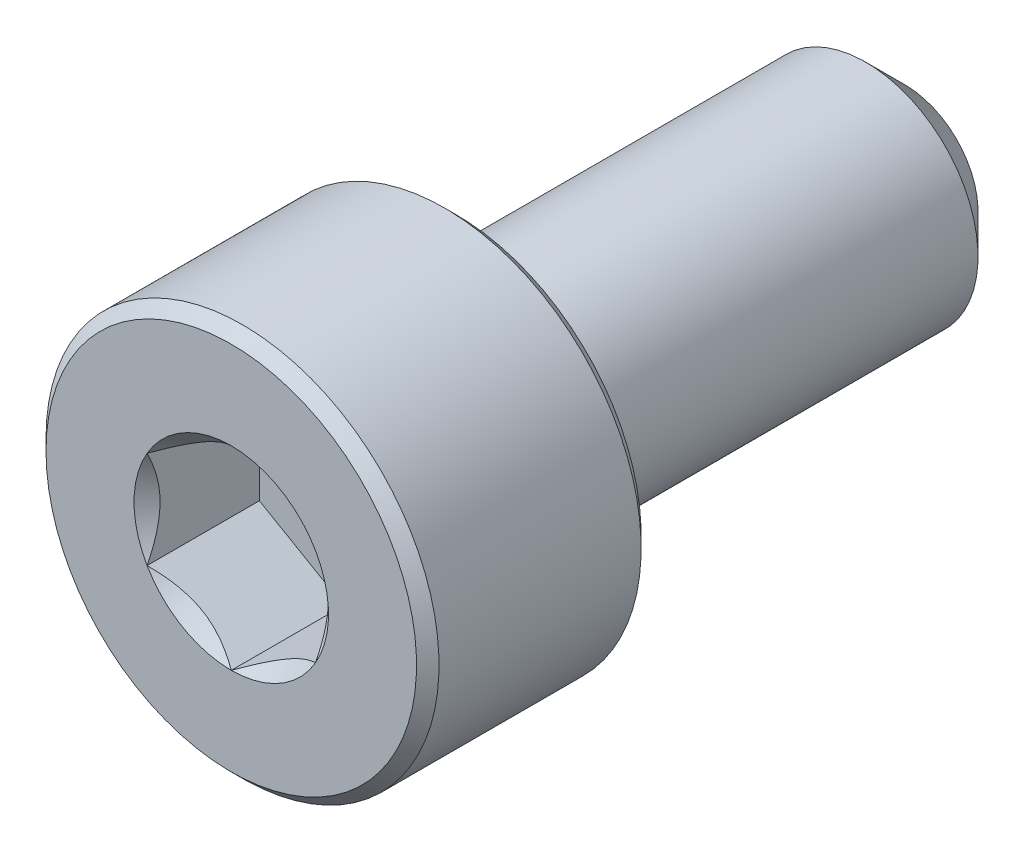
SolidWorks part; units mm, degrees
material "Alloy Steel"
ref_plane "Front Plane" through (0, 0, 0) normal (0, 0, 1) x (1, 0, 0)
ref_plane "Top Plane" through (0, 0, 0) normal (0, 1, 0) x (1, 0, 0)
ref_plane "Right Plane" through (0, 0, 0) normal (1, 0, 0) x (0, 0, -1)
sketch "Sketch1" plane through (0, 0, 0) normal (1, 0, 0) x (0, 0, -1)
  line L0 (-6, 0) -> (6, 0) construction
  line L1 (6, 0) -> (6, 1.3) construction
  line L2 (6, 1.3) -> (5.3, 2) construction
  line L3 (5.3, 2) -> (-2, 2) construction
  line L5 (-2, 2) -> (-2, 3.5) construction
  line L6 (-2, 3.5) -> (-6, 3.5) construction
  line L7 (-6, 3.5) -> (-6, 0) construction
  line L8 (6, 1.3) -> (6, 2) construction
  line L9 (5.9563, 2.0758) -> (6.3063, 1.4696) construction
  line L10 (6.3063, 1.4696) -> (6.6563, 2.0758) construction
  line L11 (6.6563, 2.0758) -> (5.9563, 2.0758) construction
  line L12 (6.3063, 2.0758) -> (6.3063, 2) construction
  line L13 (6.3063, 1.4696) -> (6.3063, 1.5453) construction
  line L14 (6.2625, 1.5453) -> (6.35, 1.5453) construction
  line L15 (6, 2) -> (6.6125, 2) construction
  line L16 (5.9781, 2.0379) -> (6.6344, 2.0379) construction
  line L17 (6, 0) -> (6, -2) construction
  line L18 (-2.2, 3.5) -> (-2, 3.3) construction
  line L19 (-5.8, 3.5) -> (-6, 3.3) construction
  point P0 (-6, 1.5)
  point P3 (3.55, 2)
  point P4 (0, 0)
  point P22 (6.3063, 1.5453)
  point P24 (-2, 2)
  point P25 (6.3063, 2)
  point P28 (6.3063, 2.0379)
  point P29 (3.55, -2)
  point P31 (-4, 3.5)
  point P37 (-2.7, 3.5)
  point P38 (-5.7, 3.5)
  point P41 (-4, 0)
  dimension "head height" = 4
  dimension "D1" = 45
  dimension "Head Diameter" = 7
  dimension "Thread Size" = 4
  dimension "drive size" = 3
  dimension "Thread Pitch" = 0.7
  dimension "D2" = 0.0875
  dimension "D3" = 0.7
  dimension "D4" = 2.45
  dimension "D7" = 0.2
  dimension "D8" = 0.2
  dimension "D9" = 0.2
  dimension "D10" = 0.1
  dimension "D11" = 0.5
  dimension "length" = 8
  dimension "Drive Depth" = 2
sketch "Sketch2" plane through (0, 0, 0) normal (1, 0, 0) x (0, 0, -1)
  line L1 (-5.8, 3.5) -> (-2.2, 3.5)
  line L4 (5.3, 2) -> (6, 1.3)
  line L5 (6, 1.3) -> (6, 0)
  line L6 (-2.2, 3.5) -> (-2, 3.3) construction
  line L7 (6, 0) -> (-6, 0)
  line L8 (-5.8, 3.5) -> (-6, 3.3) construction
  line L9 (-2.2, 3.5) -> (-2, 3.3)
  line L10 (-5.8, 3.5) -> (-6, 3.3)
  line L11 (-6, 3.3) -> (-6, 0)
  line L12 (-2, 3.3) -> (-2, 2)
  line L13 (-2, 2) -> (5.3, 2)
revolve "Revolve1" add sketch "Sketch2" angle 360 about L7
sketch "Sketch3" plane through (0, 0, 6) normal (0, 0, 1) x (1, 0, 0)
  line L1 (0, 1.7321) -> (-1.5, 0.866)
  line L2 (-1.5, 0.866) -> (-1.5, -0.866)
  line L3 (-1.5, -0.866) -> (0, -1.7321)
  line L4 (0, -1.7321) -> (1.5, -0.866)
  line L5 (1.5, -0.866) -> (1.5, 0.866)
  line L6 (1.5, 0.866) -> (0, 1.7321)
  circle A0 centre (0, 0) radius 1.5 construction
  dimension "D1" = 3
extrude "Cut-Extrude1" cut sketch "Sketch3" against normal up to vertex (2 mm away) up to point (0, 0, 4)
sketch "Sketch4" plane through (0, 0, 6) normal (0, 0, 1) x (1, 0, 0)
  circle A0 centre (0, 0) radius 1.7321
extrude "Cut-Extrude2" cut sketch "Sketch4" against normal blind 0.5 draft 45
ref_plane "Plane1" [suppressed] through (0, 0, 2) normal (0, 0, 1) x (1, 0, 0)
split "Split1" [suppressed] bodies to split 106
sketch "Sketch6" [suppressed] plane through (0, 0, -6) normal (0, 0, -1) x (-1, 0, 0)
  circle A0 centre (0, 0) radius 2
curve "Helix/Spiral1" [suppressed] pitch 0.7 height 8.7 turns 12.4286
sketch "Sketch7" [suppressed] plane through (0, 0, 0) normal (1, 0, 0) x (0, 0, -1)
  line L0 (5.9781, 2.0379) -> (6.6344, 2.0379)
  line L1 (6.6344, 2.0379) -> (6.35, 1.5453)
  line L2 (6.35, 1.5453) -> (6.2625, 1.5453)
  line L3 (6.2625, 1.5453) -> (5.9781, 2.0379)
sweep "Cut-Sweep1" [suppressed] cut profiles "Sketch7" path "Helix/Spiral1"
sketch "Sketch8" [suppressed] plane through (0, 0, 2) normal (0, 0, -1) x (-1, 0, 0)
  circle A0 centre (0, 0) radius 2
extrude "Boss-Extrude1" [suppressed] add sketch "Sketch8" along normal through all draft 45
ref_plane "Plane2" [suppressed] through (0, 0, 4) normal (0, 0, 1) x (1, 0, 0)
sketch "Sketch9" [suppressed] plane through (0, 0, 4) normal (0, 0, 1) x (1, 0, 0)
  line L0 (0, 3.4038) -> (0.0916, 3.4988)
  line L1 (0, 3.4038) -> (-0.0916, 3.4988)
  line L2 (0, 3.5) -> (0, 0) construction
  line L3 (-0.0916, 3.4988) -> (0, 0) construction
  line L4 (0, 0) -> (0.0916, 3.4988) construction
  arc A0 (0.0916, 3.4988) -> (-0.0916, 3.4988) centre (0, 0) ccw
  circle A1 centre (0, 0) radius 3.4038 construction
  dimension "D1" = 7
  dimension "D2" = 6.8075
  dimension "D3" = 3
extrude "Cut-Extrude4" [suppressed] cut sketch "Sketch9" against normal up to vertex and the other way up to vertex up to point (0, 3.5, 2.7) other way up to point (0, 3.5, 5.7)
pattern_circular "CirPattern2" [suppressed] count 96 over 360 about axis through (0, 0, 6) along (0, 0, -1) of bodies 113
equation "\"D2@Sketch1\" = \"Thread Pitch@Sketch1\" / 8"
equation "\"D3@Sketch1\" = \"Thread Pitch@Sketch1\""
equation "\"D3@Helix/Spiral1\" = \"length@Sketch1\" + \"Thread Pitch@Sketch1\""
equation "\"D4@Helix/Spiral1\" = \"Thread Pitch@Sketch1\""
equation "\"D4@Sketch1\" = \"Thread Pitch@Sketch1\" * 3.5"
equation "\"D7@Sketch1\"=\"head height@Sketch1\"*.05"
equation "\"D8@Sketch1\"=\"D7@Sketch1\""
equation "\"D9@Sketch1\"=\"D7@Sketch1\""
equation "\"D10@Sketch1\"=\"D7@Sketch1\"/2"
equation "\"D11@Sketch1\"=\"D10@Sketch1\"*5"
equation "\"D1@CirPattern2\"=( 360 / \"D3@Sketch9\" )*0.8"
equation "\"D1@Sketch3\" = \"drive size@Sketch1\""
equation "\"D2@Sketch9\"=\"Head Diameter@Sketch1\" * 0.9725"
